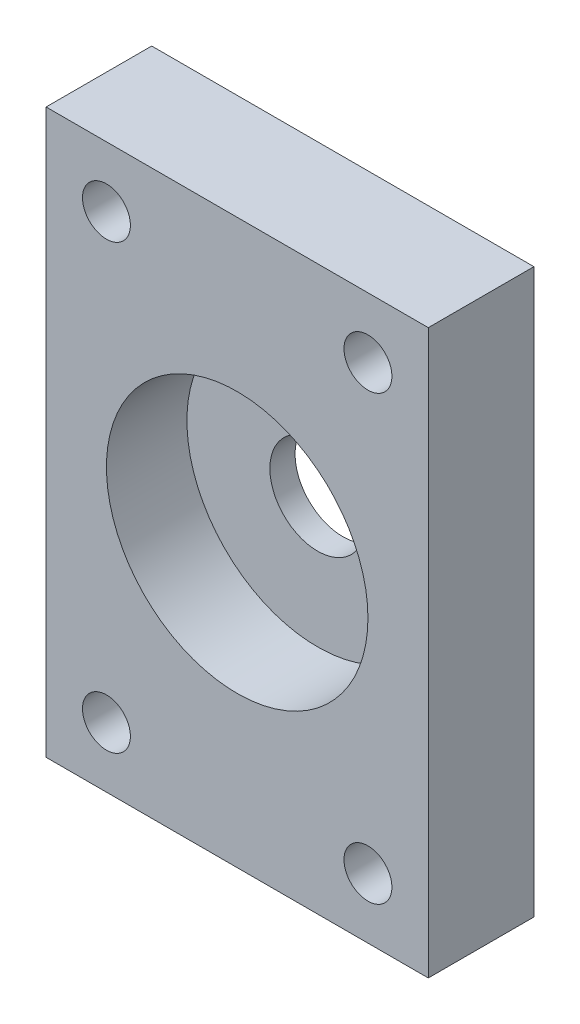
SolidWorks part; units mm, degrees
ref_plane "Alzado" through (0, 0, 0) normal (0, 0, 1) x (1, 0, 0)
ref_plane "Planta" through (0, 0, 0) normal (0, 1, 0) x (1, 0, 0)
ref_plane "Vista lateral" through (0, 0, 0) normal (1, 0, 0) x (0, 0, -1)
sketch "Croquis1" plane through (0, 0, 0) normal (0, 0, 1) x (1, 0, 0)
  circle A0 centre (0, 0) radius 13
  circle A1 centre (0, 0) radius 18
  dimension "D1" = 26
  dimension "D2" = 5
extrude "Saliente-Extruir1" add sketch "Croquis1" along normal blind 8
sketch "Croquis2" plane through (0, 0, 0) normal (0, 0, -1) x (-1, 0, 0)
  line L1 (-19, -28) -> (19, -28)
  line L2 (-19, -28) -> (-19, 28)
  line L3 (-19, 28) -> (19, 28)
  line L4 (19, -28) -> (19, 28)
  line L5 (-19, -28) -> (19, 28) construction
  line L6 (-19, 28) -> (19, -28) construction
  circle A0 centre (0, 0) radius 18 construction
  circle A1 centre (0, 0) radius 18
  point P0 (0, 0)
  dimension "D1" = 38
  dimension "D2" = 56
extrude "Saliente-Extruir2" add sketch "Croquis2" against normal blind 8
sketch "Croquis5" plane through (0, 0, 0) normal (0, 0, -1) x (-1, 0, 0)
  line L4 (19, -28) -> (19, 28)
  line L5 (19, 28) -> (-19, 28)
  line L6 (-19, 28) -> (-19, -28)
  line L7 (-19, -28) -> (19, -28)
  line L8 (19, -28) -> (19, 28)
  line L9 (19, 28) -> (-19, 28)
  line L10 (-19, 28) -> (-19, -28)
  line L11 (-19, -28) -> (19, -28)
  circle A0 centre (0, 0) radius 4.75
  dimension "D2" = 9.5
  dimension "D1" = 0
extrude "Saliente-Extruir3" add sketch "Croquis5" along normal blind 2.5
sketch "Croquis7" plane through (0, 0, -2.5) normal (0, 0, -1) x (-1, 0, 0)
  line L0 (25.83, 0) -> (-30.4698, 0) construction
  line L1 (0, 25.0731) -> (0, -24.2875) construction
  line L2 (19, 28) -> (-19, 28) construction
  line L3 (-19, 28) -> (-19, -28) construction
  circle A0 centre (-13, 22) radius 2.3813
  circle A1 centre (13, 22) radius 2.3813
  circle A2 centre (13, -22) radius 2.3813
  circle A3 centre (-13, -22) radius 2.3813
  dimension "D3" = 4.7625
  dimension "D1" = 6
  dimension "D2" = 6
extrude "Cortar-Extruir3" cut sketch "Croquis7" against normal through all
